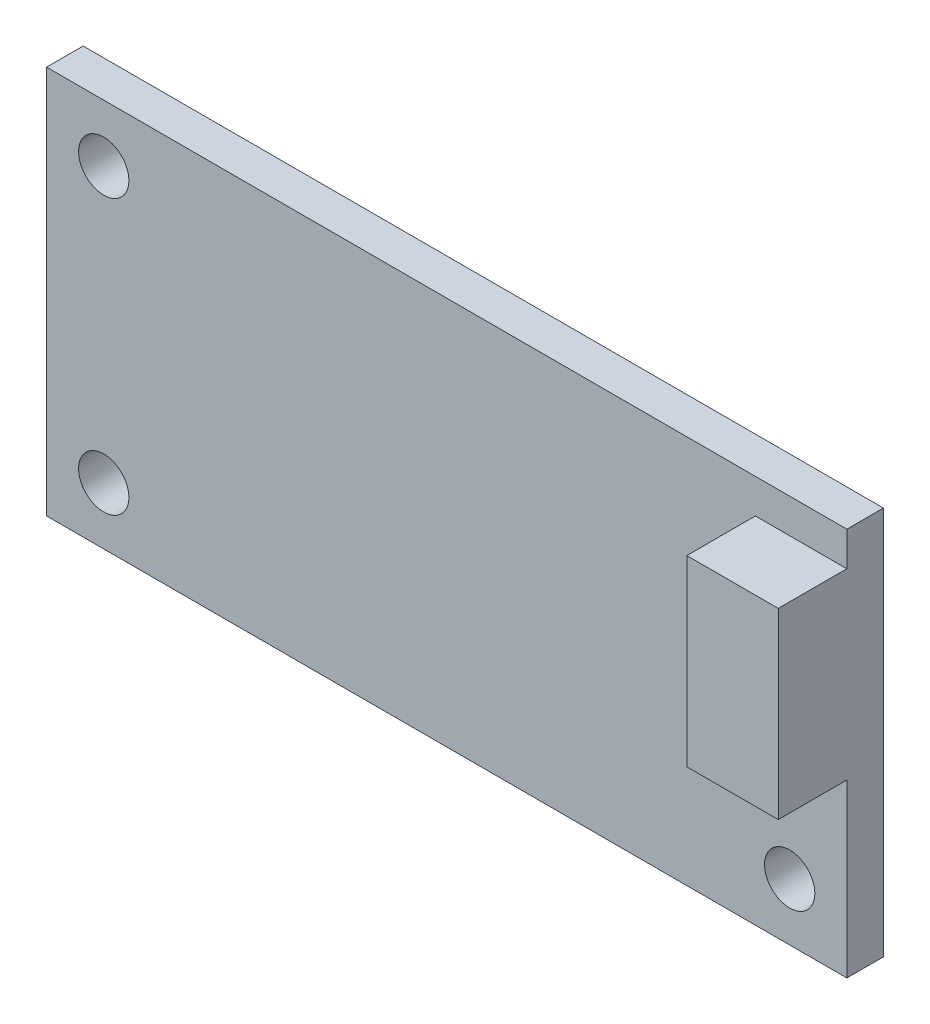
SolidWorks part; units mm, degrees
ref_plane "Front Plane" through (0, 0, 0) normal (0, 0, 1) x (1, 0, 0)
ref_plane "Top Plane" through (0, 0, 0) normal (0, 1, 0) x (1, 0, 0)
ref_plane "Right Plane" through (0, 0, 0) normal (1, 0, 0) x (0, 0, -1)
sketch "Sketch1" plane through (0, 0, 0) normal (0, 0, 1) x (1, 0, 0)
  line L1 (-17.5, 8.5) -> (17.5, 8.5)
  line L2 (-17.5, 8.5) -> (-17.5, -8.5)
  line L3 (-17.5, -8.5) -> (17.5, -8.5)
  line L4 (17.5, 8.5) -> (17.5, -8.5)
  line L5 (-17.5, 8.5) -> (17.5, -8.5) construction
  line L6 (-17.5, -8.5) -> (17.5, 8.5) construction
  point P0 (0, 0)
  dimension "D1" = 17
  dimension "D2" = 35
extrude "Boss-Extrude1" add sketch "Sketch1" along normal blind 1.6
sketch "Sketch2" plane through (0, 0, 1.6) normal (0, 0, 1) x (1, 0, 0)
  line L0 (-17.5, 8.5) -> (-17.5, -8.5) construction
  line L1 (-17.5, -8.5) -> (17.5, -8.5) construction
  line L2 (17.5, 8.5) -> (-17.5, 8.5) construction
  line L3 (17.5, -8.5) -> (17.5, 8.5) construction
  circle A0 centre (-15, -6) radius 1.1
  circle A1 centre (-15, 6) radius 1.1
  circle A2 centre (15, -6) radius 1.1
  point P10 (0, 0)
  point P11 (0, 0)
  dimension "D3" = 2.2
  dimension "D1" = 2.5
  dimension "D2" = 2.5
  dimension "D4" = 2.5
  dimension "D5" = 2.5
extrude "Cut-Extrude1" cut sketch "Sketch2" against normal up to surface (1.6 mm away) up to face at (0, 0, 0)
sketch "Sketch3" plane through (0, 0, 1.6) normal (0, 0, 1) x (1, 0, 0)
  line L0 (17.5, 8.5) -> (-17.5, 8.5) construction
  line L1 (17.5, 7) -> (13.5, 7)
  line L2 (17.5, 7) -> (17.5, -1)
  line L3 (17.5, -1) -> (13.5, -1)
  line L4 (13.5, 7) -> (13.5, -1)
  line L5 (17.5, -8.5) -> (17.5, 8.5) construction
  dimension "D1" = 1.5
  dimension "D2" = 8
  dimension "D3" = 4
extrude "Boss-Extrude2" add sketch "Sketch3" along normal blind 3
